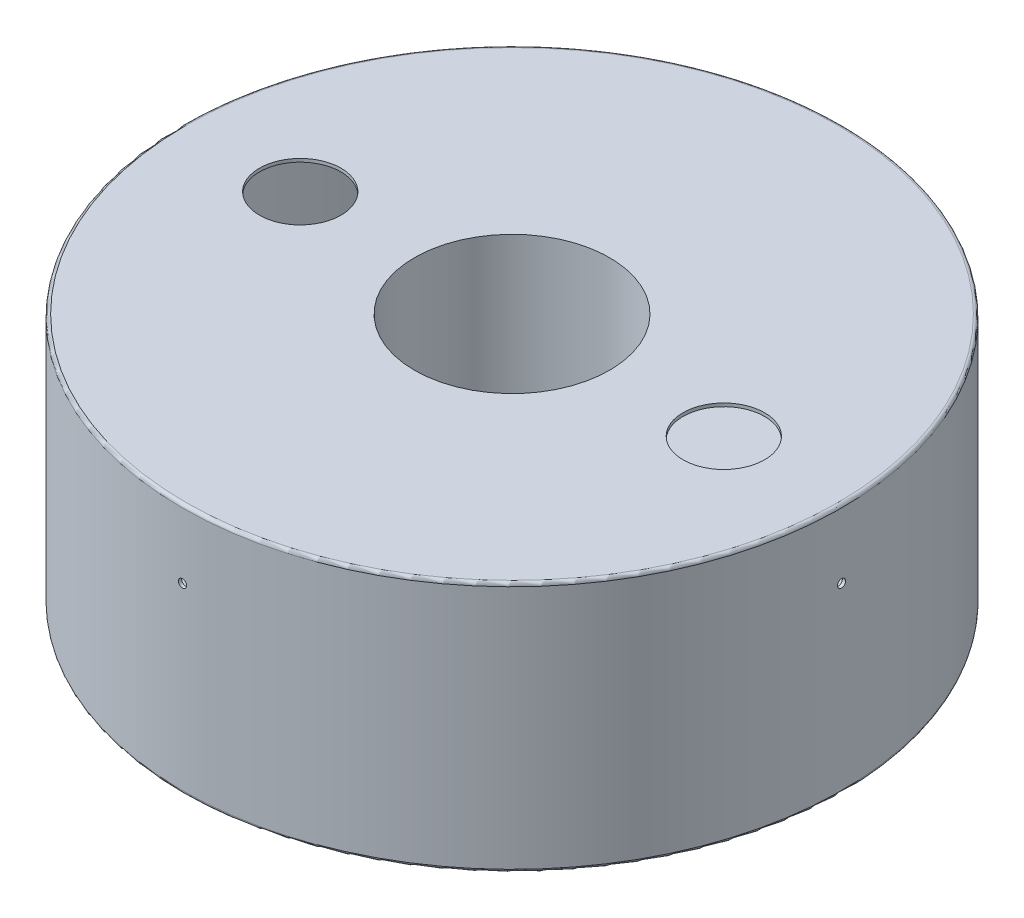
SolidWorks part; units mm, degrees
material "2014 Alloy"
ref_plane "Front Plane" through (0, 0, 0) normal (0, 0, 1) x (1, 0, 0)
ref_plane "Top Plane" through (0, 0, 0) normal (0, 1, 0) x (1, 0, 0)
ref_plane "Right Plane" through (0, 0, 0) normal (1, 0, 0) x (0, 0, -1)
sketch "Sketch9" plane through (0, 0, 0) normal (0, 1, 0) x (1, 0, 0)
  circle A0 centre (0, 0) radius 2000
extrude "Boss-Extrude5" add sketch "Sketch9" along normal blind 1500
sketch "Sketch10" plane through (0, 1500, 0) normal (0, 1, 0) x (1, 0, 0)
  circle A0 centre (0, 0) radius 598.217
extrude "Cut-Extrude3" cut sketch "Sketch10" against normal blind 1500
shell "Shell6" thickness 20 removed face at (0, 0, 598.217) outward yes
sketch "Sketch11" plane through (0, 1520, 0) normal (0, 1, 0) x (1, 0, 0)
  circle A0 centre (0, 0) radius 598.217
extrude "Boss-Extrude6" add sketch "Sketch11" against normal through all
sketch "Sketch13" plane through (0, 1520, 0) normal (0, 1, 0) x (1, 0, 0)
  circle A0 centre (0, 0) radius 618.217
extrude "Boss-Extrude7" add sketch "Sketch13" against normal through all
sketch "Sketch14" plane through (0, 1520, 0) normal (0, 1, 0) x (1, 0, 0)
  circle A0 centre (0, 0) radius 598.217
extrude "Cut-Extrude5" cut sketch "Sketch14" against normal through all
fillet "Fillet2" radius 20 2 edges at (0, 1520, 2020) (0, -20, 2020)
sketch "Sketch16" plane through (0, 1520, 0) normal (0, 1, 0) x (1, 0, 0)
  circle A0 centre (-1298.217, 0) radius 250
  circle A1 centre (1298.217, 0) radius 250
  dimension "D1" = 2
extrude "Cut-Extrude6" cut sketch "Sketch16" against normal blind 547 and the other way through all
sketch "Sketch19" plane through (0, 0, 0) normal (0, 0, 1) x (1, 0, 0)
  circle A0 centre (0, 1100) radius 24.963
extrude "Cut-Extrude11" cut sketch "Sketch19" along normal blind 300 and the other way blind 100 from offset 1800
pattern_circular "CirPattern1" count 4 every 90 about axis through (0, 1520, 0) along (0, 1, 0) of "Cut-Extrude11"
